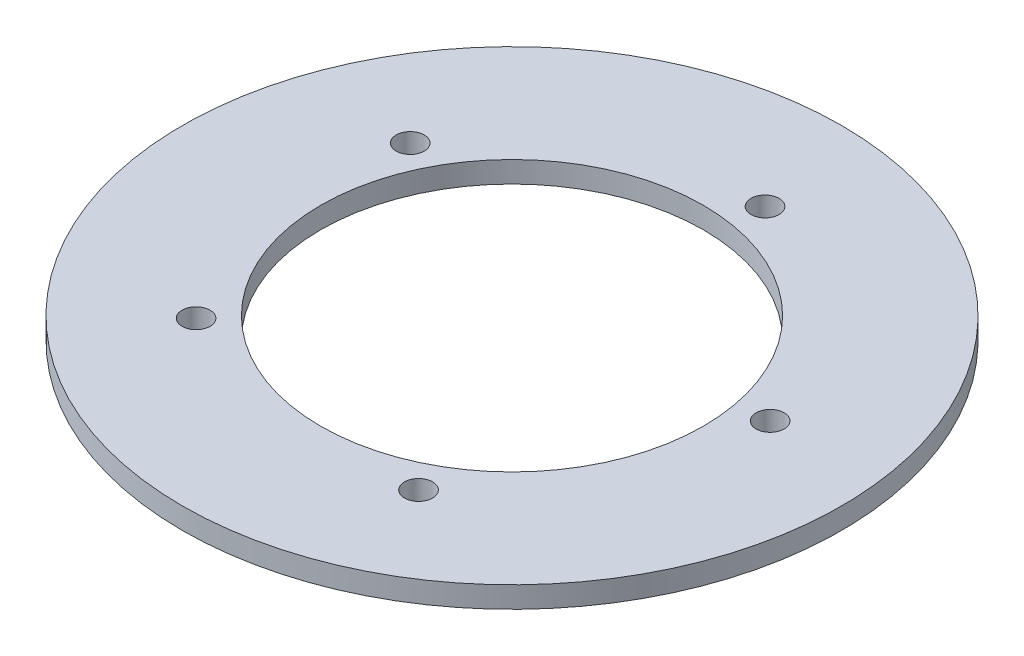
SolidWorks part; units mm, degrees
ref_plane "Front Plane" through (0, 0, 0) normal (0, 0, 1) x (1, 0, 0)
ref_plane "Top Plane" through (0, 0, 0) normal (0, 1, 0) x (1, 0, 0)
ref_plane "Right Plane" through (0, 0, 0) normal (1, 0, 0) x (0, 0, -1)
sketch "Sketch1" plane through (0, 0, 0) normal (0, 1, 0) x (1, 0, 0)
  circle A0 centre (0, 0) radius 77.5
  circle A1 centre (0, 0) radius 45
  dimension "D1" = 155
  dimension "D2" = 90
extrude "Body" add sketch "Sketch1" along normal blind 5
hole_wizard "M6 Clearance Hole1" positions "Sketch2" profile "Sketch3" hole size "M6" standard "ANSI Metric" end condition through all
sketch "Sketch2" plane through (0, 5, 0) normal (0, 1, 0) x (1, 0, 0)
  point P0 (7.5, 52)
  point P10 (51.7726, 8.936)
  point P11 (24.4972, -46.4773)
  point P12 (-36.6325, -37.6605)
  point P13 (-47.1373, 23.2018)
  point P15 (0, 0)
  dimension "D1" = 52
  dimension "D2" = 7.5
  dimension "D3" = 5
sketch "Sketch3" plane through (7.5, 5, -52) normal (1, 0, 0) x (0, 0, 1)
  line L0 (0, 0) -> (0, 5)
  line L1 (0, 5) -> (3.3, 5)
  line L2 (3.3, 5) -> (3.3, 0)
  line L5 (3.3, 0) -> (0, 0)
  line L11 (0, -6.35) -> (0, 107.95) construction
  dimension "Thru Hole Dia." = 6.6
  dimension "Thru Hole Depth" = 5
